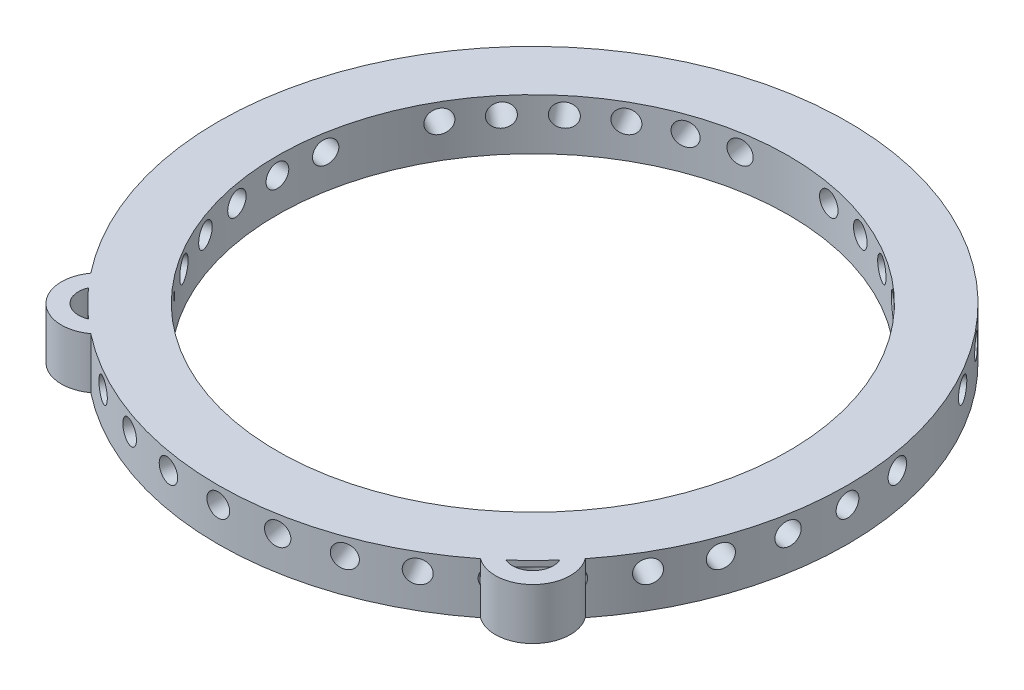
SolidWorks part; units mm, degrees
material "ABS"
ref_plane "Alzado" through (0, 0, 0) normal (0, 0, 1) x (1, 0, 0)
ref_plane "Planta" through (0, 0, 0) normal (0, 1, 0) x (1, 0, 0)
ref_plane "Vista lateral" through (0, 0, 0) normal (1, 0, 0) x (0, 0, -1)
sketch "Croquis2" plane through (0, 0, 0) normal (0, 0, 1) x (1, 0, 0)
  line L0 (0, 0) -> (-22.5, 0) construction
  line L1 (-22.5, 0) -> (-22.5, 1)
  line L2 (-22.5, 1) -> (-22.5, 4.5)
  line L3 (-22.5, 0) -> (-27.7, 0)
  line L4 (-27.7, 0) -> (-27.7, 4.5)
  line L5 (-27.7, 4.5) -> (-22.5, 4.5)
  line L6 (0, 0) -> (0, 4.6512) construction
  dimension "D1" = 22.5
  dimension "D2" = 1
  dimension "D3" = 3.5
  dimension "D4" = 27.7
revolve "Revolución1" add sketch "Croquis2" angle 360 about L6
ref_plane "Plano1" through (27.7, 0, 0) normal (1, 0, 0) x (0, 0, -1)
sketch "Croquis3" plane through (27.7, 0, 0) normal (1, 0, 0) x (0, 0, -1)
  line L0 (0, 4) -> (0, 4.5) construction
  line L1 (27.7, 4.5) -> (-27.7, 4.5) construction
  circle A0 centre (0, 3) radius 1
  point P4 (0, 0)
  dimension "D1" = 3
  dimension "D2" = 2
  dimension "D3" = 0.5
ref_plane "Plano2" through (0, 0, 0) normal (0, 0, -1) x (-1, 0, 0)
sketch "Croquis4" plane through (0, 0, 0) normal (0, 0, -1) x (-1, 0, 0)
  line L0 (-27.7, 3) -> (-22.5038, 0) construction
  line L1 (-22.5038, 0) -> (-27.7, 0) construction
  dimension "D1" = 30
extrude "Cortar-Extruir1" cut sketch "Croquis3" against normal up to surface (5.2222 mm away)
pattern_circular "MatrizC1" count 36 over 360 about axis through (0, 0, 0) along (0, -1, 0) of "Cortar-Extruir1"
sketch "Croquis5" plane through (0, 0, 0) normal (0, -1, 0) x (1, 0, 0)
  line L0 (0, 0) -> (-19.0919, 19.0919) construction
  line L2 (0, 0) -> (0, -25.1) construction
  line L3 (0, 0) -> (-23.5863, -8.5847) construction
  circle A2 centre (0, -25.1) radius 1.8
  circle A6 centre (0, 0) radius 25.1 construction
  circle A9 centre (-23.5863, -8.5847) radius 1.8
  circle A10 centre (-19.0919, 19.0919) radius 1.8
  circle A11 centre (19.0919, 19.0919) radius 1.8
  circle A12 centre (23.5863, -8.5847) radius 1.8
  point P18 (0, 0)
  dimension "D1" = 3.6
  dimension "D2" = 50.2
  dimension "D4" = 3.6
  dimension "D7" = 3.6
  dimension "D3" = 70
  dimension "D5" = 27
  dimension "D6" = 135
extrude "Cortar-Extruir2" cut sketch "Croquis5" against normal blind 4
sketch "Croquis6" plane through (0, 0, 0) normal (0, -1, 0) x (1, 0, 0)
  line L0 (0, 0) -> (0, -22.5) construction
  line L1 (-19.0919, 20.8919) -> (-19.0919, 22.3919) construction
  circle A0 centre (-19.0919, 19.0919) radius 1.8
  circle A2 centre (0, 0) radius 22.5 construction
  circle A3 centre (19.0919, 19.0919) radius 1.8
  circle A5 centre (0, 0) radius 30.3 construction
  circle A6 centre (-19.0919, 19.0919) radius 3.3
  circle A7 centre (19.0919, 19.0919) radius 3.3
  circle A11 centre (-19.0919, 19.0919) radius 1.8 construction
  dimension "D1" = 1.5
extrude "Saliente-Extruir1" add sketch "Croquis6" against normal blind 3
sketch "Croquis8" plane through (0, 0, 0) normal (0, -1, 0) x (1, 0, 0)
  line L0 (24.3955, -5.9052) -> (26.9225, -6.5169)
  line L1 (24.3955, -5.9052) -> (24.1409, -6.8723) construction
  line L2 (24.3955, -5.9052) -> (21.8684, -5.2935)
  line L3 (22.4838, -11.1574) -> (24.8128, -12.3132)
  line L4 (22.4838, -11.1574) -> (22.9104, -10.253) construction
  line L5 (22.4838, -11.1574) -> (20.1548, -10.0017)
  line L6 (0, 0) -> (0, -25.1) construction
  line L7 (-22.4838, -11.1574) -> (-22.9104, -10.253) construction
  line L8 (-24.3955, -5.9052) -> (-24.1409, -6.8723) construction
  line L13 (2.7946, -24.9439) -> (3.0841, -27.5278)
  line L14 (2.7946, -24.9439) -> (1.7988, -25.0355) construction
  line L15 (2.7946, -24.9439) -> (2.5052, -22.3601)
  line L16 (21.7564, 17.145) -> (17.6721, 13.9264)
  line L17 (17.145, 21.7564) -> (13.9264, 17.6721)
  line L18 (-17.145, 21.7564) -> (-13.9264, 17.6721)
  line L19 (-21.7564, 17.145) -> (-17.6721, 13.9264)
  line L20 (-22.4838, -11.1574) -> (-20.1548, -10.0017)
  line L21 (-22.4838, -11.1574) -> (-24.8128, -12.3132)
  line L22 (-24.3955, -5.9052) -> (-21.8684, -5.2935)
  line L23 (-24.3955, -5.9052) -> (-26.9225, -6.5169)
  line L24 (-2.5052, -22.3601) -> (-2.7946, -24.9439)
  line L25 (-2.7946, -24.9439) -> (-3.0841, -27.5278)
  line L26 (-2.7946, -24.9439) -> (-1.7988, -25.0355) construction
  circle A0 centre (0, 0) radius 25.1 construction
  arc A1 (-21.7564, 17.145) -> (21.7564, 17.145) centre (0, 0) ccw construction
  circle A2 centre (23.5863, -8.5847) radius 1.8 construction
  circle A3 centre (0, 0) radius 22.5 construction
  circle A4 centre (0, 0) radius 22.5 construction
  arc A5 (26.9225, -6.5169) -> (24.8128, -12.3132) centre (0, 0) cw
  arc A6 (21.8684, -5.2935) -> (20.1548, -10.0017) centre (0, 0) cw
  circle A9 centre (0, -25.1) radius 1.8 construction
  arc A10 (17.145, 21.7564) -> (21.7564, 17.145) centre (19.0919, 19.0919) cw
  arc A11 (13.9264, 17.6721) -> (17.6721, 13.9264) centre (0, 0) cw
  circle A12 centre (19.0919, 19.0919) radius 1.8
  circle A13 centre (19.0919, 19.0919) radius 1.8 construction
  circle A14 centre (23.5863, -8.5847) radius 1.8
  circle A15 centre (-23.5863, -8.5847) radius 1.8
  circle A16 centre (-19.0919, 19.0919) radius 1.8
  arc A17 (-13.9264, 17.6721) -> (-17.6721, 13.9264) centre (0, 0) ccw
  arc A18 (-17.145, 21.7564) -> (-21.7564, 17.145) centre (-19.0919, 19.0919) ccw
  arc A19 (-21.8684, -5.2935) -> (-20.1548, -10.0017) centre (0, 0) ccw
  arc A20 (-26.9225, -6.5169) -> (-24.8128, -12.3132) centre (0, 0) ccw
  circle A21 centre (0, -25.1) radius 1.8
  arc A22 (2.5052, -22.3601) -> (-2.5052, -22.3601) centre (0, 0) cw
  arc A23 (3.0841, -27.5278) -> (-3.0841, -27.5278) centre (0, 0) cw
  dimension "D1" = 1
  dimension "D2" = 1
  dimension "D3" = 1
  dimension "D4" = 1
extrude "Saliente-Extruir3" add sketch "Croquis8" against normal up to surface (4.5 mm away) up to face at (0, 4.5, -27.7)
